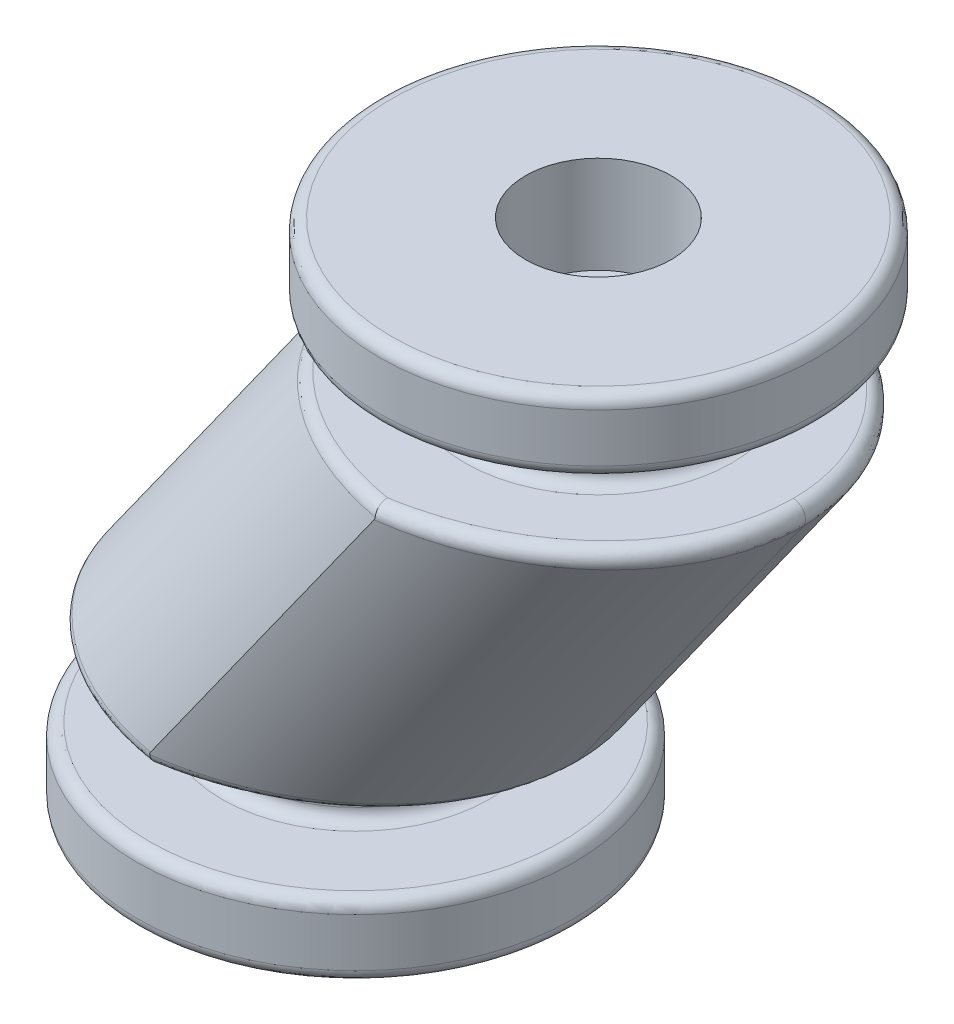
SolidWorks part; units mm, degrees
ref_plane "Front Plane" through (0, 0, 0) normal (0, 0, 1) x (1, 0, 0)
ref_plane "Top Plane" through (0, 0, 0) normal (0, 1, 0) x (1, 0, 0)
ref_plane "Right Plane" through (0, 0, 0) normal (1, 0, 0) x (0, 0, -1)
sketch "Sketch1" plane through (0, 0, 0) normal (0, 0, 1) x (1, 0, 0)
  line L1 (-4.5, -3.5) -> (4.5, -3.5)
  line L5 (-4.5, -3.5) -> (4.5, 3.5) construction
  line L6 (-1.2857, 1) -> (4.5, -3.5) construction
  line L7 (0.5, 4.9865) -> (0.5, -4.7824) construction
  line L9 (-4.5, -3.5) -> (0.5, 3.5)
  line L10 (4.5, -3.5) -> (9.5, 3.5)
  line L11 (0.5, 3.5) -> (9.5, 3.5)
  point P0 (0, 0)
  dimension "D1" = 7
  dimension "D2" = 9
extrude "Boss-Extrude2" add sketch "Sketch1" along normal blind 9
fillet "Fillet1" radius 4.5 4 edges at (7, 0, 9) (-2, 0, 9) (-2, 0, 0) (7, 0, 0)
sketch "Sketch2" plane through (0, 3.5, 0) normal (0, 1, 0) x (1, 0, 0)
  line L0 (0.5, -4.5) -> (9.5, -4.5) construction
  line L1 (5, -0.0788) -> (5, -8.9212) construction
  circle A0 centre (5, -4.5) radius 2.5
  ellipse E0 centre (3.9699, -4.5) end of major axis (9.5, -4.5) minor radius 4.5 (9.5, -4.5) -> (5, -0.0788) ccw construction
  ellipse E1 centre (3.9699, -4.5) end of major axis (9.5, -4.5) minor radius 4.5 (5, -8.9212) -> (9.5, -4.5) ccw construction
extrude "Boss-Extrude3" add sketch "Sketch2" along normal blind 1.5
sketch "Sketch3" plane through (0, 5, 0) normal (0, 1, 0) x (1, 0, 0)
  circle A0 centre (5, -4.5) radius 4.5
extrude "Boss-Extrude4" add sketch "Sketch3" along normal blind 1.5
sketch "Sketch4" plane through (0, -3.5, 0) normal (0, -1, 0) x (-1, 0, 0)
  line L0 (0, -0.0788) -> (0, -8.9212) construction
  line L1 (-4.5, -4.5) -> (4.5, -4.5) construction
  circle A0 centre (0, -4.5) radius 2.5
extrude "Boss-Extrude5" add sketch "Sketch4" along normal blind 1.5
sketch "Sketch5" plane through (0, -5, 0) normal (0, -1, 0) x (-1, 0, 0)
  circle A0 centre (0, -4.5) radius 4.5
extrude "Boss-Extrude6" add sketch "Sketch5" along normal blind 1.5
fillet "Fillet2" radius 0.25 16 edges at (0, -6.5, 0) (1.7711, 3.5, 7.3704) (8.2289, 3.5, 1.6296) (-3.2289, -3.5, 7.3704) (3.2289, -3.5, 7.3704) (5, 5, 7) (5, 3.5, 2) (0, -5, 2) (0, -3.5, 7) (5, 6.5, 9) (5, 5, 9) (1.7711, 3.5, 1.6296) (8.2289, 3.5, 7.3704) (-3.2289, -3.5, 1.6296) (3.2289, -3.5, 1.6296) (0, -5, 0)
sketch "Sketch6" plane through (0, 6.5, 0) normal (0, 1, 0) x (1, 0, 0)
  circle A0 centre (5, -4.5) radius 1.5
extrude "Cut-Extrude1" cut sketch "Sketch6" against normal blind 2
sketch "Sketch7" plane through (0, -6.5, 0) normal (0, -1, 0) x (-1, 0, 0)
  circle A0 centre (0, -4.5) radius 1.5
extrude "Cut-Extrude2" cut sketch "Sketch7" against normal blind 2
